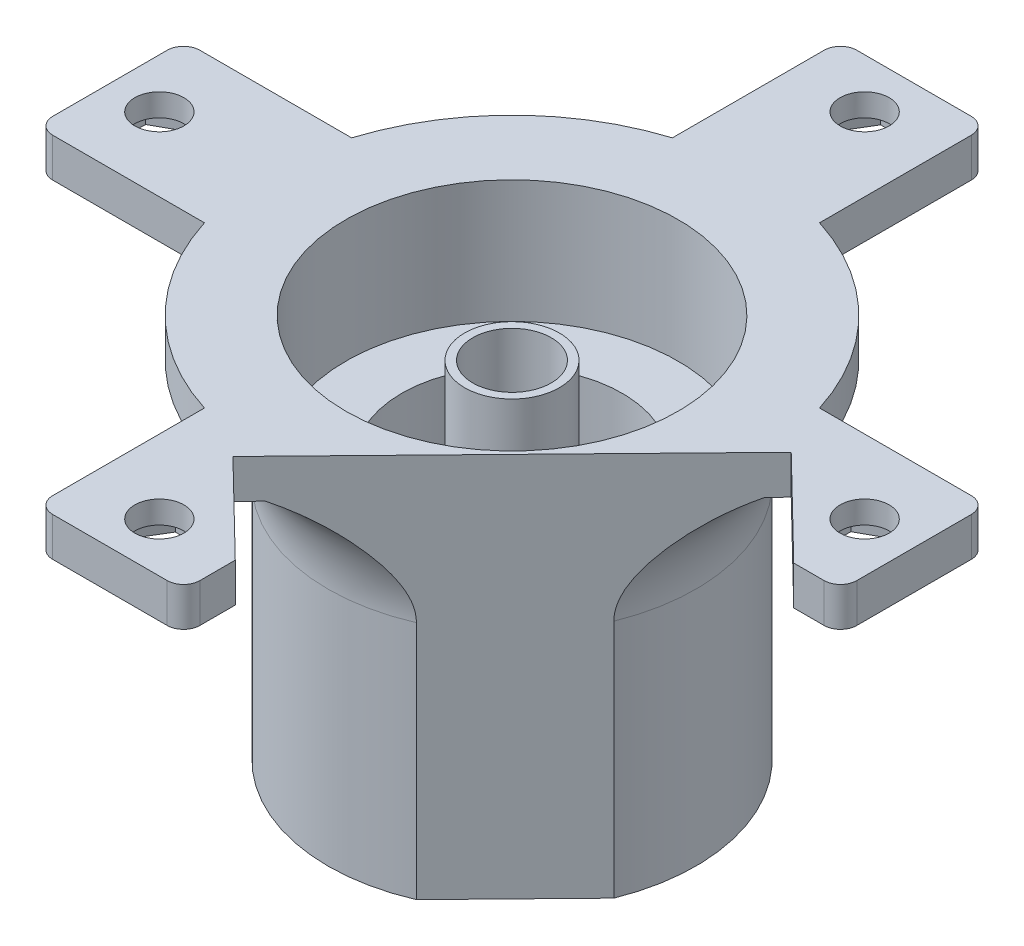
SolidWorks part; units mm, degrees
ref_plane "Front Plane" through (0, 0, 0) normal (0, 0, 1) x (1, 0, 0)
ref_plane "Top Plane" through (0, 0, 0) normal (0, 1, 0) x (1, 0, 0)
ref_plane "Right Plane" through (0, 0, 0) normal (1, 0, 0) x (0, 0, -1)
sketch "Sketch1" plane through (0, 0, 0) normal (0, 1, 0) x (1, 0, 0)
  circle A1 centre (0, 0) radius 22.5
  dimension "D2" = 45
extrude "Boss-Extrude1" add sketch "Sketch1" along normal blind 20
sketch "Sketch2" plane through (0, 20, 0) normal (0, 1, 0) x (1, 0, 0)
  circle A0 centre (0, 0) radius 22.5
  circle A1 centre (0, 0) radius 13.5
  dimension "D1" = 27
extrude "Boss-Extrude2" add sketch "Sketch2" along normal blind 20
sketch "Sketch3" plane through (0, 20, 0) normal (0, 1, 0) x (1, 0, 0)
  circle A0 centre (0, 0) radius 5.93
  dimension "D1" = 11.86
extrude "Cut-Extrude2" cut sketch "Sketch3" against normal blind 30
sketch "Sketch5" plane through (0, 0, 0) normal (0, -1, 0) x (1, 0, 0)
  line L1 (-28.6757, -6.397) -> (1.4133, -6.397)
  line L2 (-28.6757, -6.397) -> (-28.6757, 6.3734)
  line L3 (-28.6757, 6.3734) -> (1.4133, 6.3734)
  line L4 (1.4133, -6.397) -> (1.4133, 6.3734)
extrude "Cut-Extrude3" cut sketch "Sketch5" against normal blind 20
fillet "Fillet1" radius 10 2 edges at (-16.7298, 20, -6.397) (-16.7396, 20, 6.3734)
sketch "Sketch6" plane through (0, 0, 0) normal (0, -1, 0) x (1, 0, 0)
  circle A0 centre (0, 0) radius 22.5
extrude "Boss-Extrude3" add sketch "Sketch6" along normal blind 2.33
sketch "Sketch7" plane through (0, 0, 0) normal (0, 1, 0) x (1, 0, 0)
  circle A0 centre (0, 0) radius 5.8
  circle A1 centre (0, 0) radius 4.8
  dimension "D1" = 11.6
  dimension "D2" = 9.6
extrude "Boss-Extrude4" add sketch "Sketch7" along normal through all
sketch "Sketch8" plane through (0, 40, 0) normal (0, 1, 0) x (1, 0, 0)
  circle A0 centre (0, 0) radius 16
  circle A1 centre (0, 0) radius 30
  dimension "D1" = 32
  dimension "D2" = 60
extrude "Boss-Extrude5" add sketch "Sketch8" along normal blind 4.76
fillet "Fillet3" radius 15 1 edges at (0, 40, 22.5)
sketch "Sketch9" plane through (0, 44.76, 0) normal (0, 1, 0) x (1, 0, 0)
  line L0 (0, 0) -> (75.4489, 0)
  line L1 (75.4489, 0) -> (-71.7092, 0)
  line L2 (-71.7092, 0) -> (0, 0)
  line L3 (0, 0) -> (0, 61.7625)
  line L4 (0, 61.7625) -> (0, -54.9617)
  line L5 (24.1753, -9) -> (49.1753, -9)
  line L6 (9, 24.1753) -> (-9, 24.1753)
  line L7 (9, 24.1753) -> (9, 49.1753)
  line L8 (9, 49.1753) -> (-9, 49.1753)
  line L9 (-9, 24.1753) -> (-9, 49.1753)
  line L10 (24.1753, -9) -> (24.1753, 9)
  line L11 (24.1753, 9) -> (49.1753, 9)
  line L12 (49.1753, -9) -> (49.1753, 9)
  line L13 (-9, -24.1753) -> (-9, -49.1753)
  line L14 (-9, -24.1753) -> (9, -24.1753)
  line L15 (9, -24.1753) -> (9, -49.1753)
  line L16 (-9, -49.1753) -> (9, -49.1753)
  line L17 (-24.1753, 9) -> (-49.1753, 9)
  line L18 (-24.1753, 9) -> (-24.1753, -9)
  line L19 (-24.1753, -9) -> (-49.1753, -9)
  line L20 (-49.1753, 9) -> (-49.1753, -9)
  point P26 (0, 0)
  circle M7 centre (0, 0) radius 30
  dimension "D1" = 18
  dimension "D2" = 9
  dimension "D3" = 25
  dimension "D4" = 4
extrude "Boss-Extrude6" add sketch "Sketch9" against normal blind 4.76 contours L7 L8 L3 M7 | L9 L3 L8 M7 | L0 L12 L11 M7 | L5 L12 L0 M7 | L4 L16 L15 M7 | L13 L16 L4 M7 | L1 L20 L19 M7 | L17 L20 L1 M7 region at (39.3552, 44.76, -4.5525) region at (39.3552, 44.76, 4.5525) region at (-39.3552, 44.76, 4.5525) region at (-39.3552, 44.76, -4.5525) region at (-4.5525, 44.76, -39.3552) region at (4.5525, 44.76, -39.3552) region at (4.5525, 44.76, 39.3552) region at (-4.5525, 44.76, 39.3552)
sketch "Sketch13" plane through (0, 44.76, 0) normal (0, 1, 0) x (1, 0, 0)
  line L0 (0, 0) -> (0, 1.6172)
  line L1 (0, 43.1335) -> (0, -53.1995)
  line L2 (0, 0) -> (-52.7252, 0)
  line L3 (0, 0) -> (43.1335, 0)
  line L4 (43.1335, 0) -> (0, 43.1335)
  circle A0 centre (0, 43.1335) radius 3
  circle A1 centre (43.1335, 0) radius 3
  circle A2 centre (0, -43.1335) radius 3
  circle A3 centre (-43.1335, 0) radius 3
  point P18 (0, 0)
  dimension "D3" = 6
  dimension "D1" = 61
  dimension "D2" = 45
  dimension "D4" = 4
extrude "Cut-Extrude6" cut sketch "Sketch13" against normal blind 4.76 contours L1 A2 | L1 A2 | L2 A3 | L2 A3 | L3 A1 L4 | L4 A0 L1 | L1 A0 L4 | L4 A1 L3 region at (1.2732, 44.76, 43.1335) region at (-1.2732, 44.76, 43.1335) region at (-43.1335, 44.76, 1.2732) region at (-43.1335, 44.76, -1.2732) region at (41.3329, 44.76, -0.7458) region at (43.3907, 44.76, 0.1065) region at (-0.1065, 44.76, -43.3907) region at (0.7458, 44.76, -41.3329)
sketch "Sketch14" plane through (0, 44.76, 0) normal (0, 1, 0) x (1, 0, 0)
  circle A0 centre (0, 0) radius 20.32
  circle A1 centre (0, 0) radius 10
  dimension "D1" = 40.64
  dimension "D2" = 20
extrude "Cut-Extrude7" cut sketch "Sketch14" against normal blind 15
sketch "Sketch15" plane through (0, 20, 0) normal (0, 1, 0) x (1, 0, 0)
  circle A0 centre (0, 0) radius 13.5
  circle A1 centre (0, 0) radius 5.8
  circle A2 centre (0, 0) radius 5.8 construction
  dimension "D1" = 0
extrude "Cut-Extrude8" cut sketch "Sketch15" against normal blind 10
sketch "Sketch17" plane through (0, 44.76, 0) normal (0, 1, 0) x (1, 0, 0)
  line L0 (34.212, 0.0099) -> (0.5146, -34.5837)
  line L1 (34.212, 0.0099) -> (45.4754, -10.9617)
  line L2 (0.5146, -34.5837) -> (11.7781, -45.5554)
  line L3 (45.4754, -10.9617) -> (11.7781, -45.5554)
  arc A0 (-28.6182, -9) -> (-9, -28.6182) centre (0, 0) ccw construction
  dimension "D1" = 24.5
extrude "Cut-Extrude10" cut sketch "Sketch17" against normal through all
sketch "Sketch18" plane through (0, 40, 0) normal (0, -1, 0) x (-1, 0, 0)
  line L0 (47.4916, -2.3902) -> (47.3825, 2.5791)
  line L1 (2.3902, 47.4916) -> (-2.5791, 47.3825)
  line L2 (-2.5791, 47.3825) -> (-4.9693, 43.0244)
  line L3 (-4.9693, 43.0244) -> (-2.3902, 38.7754)
  line L4 (-2.3902, 38.7754) -> (2.5791, 38.8845)
  line L5 (2.5791, 38.8845) -> (4.9693, 43.2426)
  line L6 (4.9693, 43.2426) -> (2.3902, 47.4916)
  line L7 (47.3825, 2.5791) -> (43.0244, 4.9693)
  line L8 (43.0244, 4.9693) -> (38.7754, 2.3902)
  line L9 (38.7754, 2.3902) -> (38.8845, -2.5791)
  line L10 (38.8845, -2.5791) -> (43.2426, -4.9693)
  line L11 (43.2426, -4.9693) -> (47.4916, -2.3902)
  line L12 (-2.3902, -47.4916) -> (2.5791, -47.3825)
  line L13 (2.5791, -47.3825) -> (4.9693, -43.0244)
  line L14 (4.9693, -43.0244) -> (2.3902, -38.7754)
  line L15 (2.3902, -38.7754) -> (-2.5791, -38.8845)
  line L16 (-2.5791, -38.8845) -> (-4.9693, -43.2426)
  line L17 (-4.9693, -43.2426) -> (-2.3902, -47.4916)
  line L18 (-47.4916, 2.3902) -> (-47.3825, -2.5791)
  line L19 (-47.3825, -2.5791) -> (-43.0244, -4.9693)
  line L20 (-43.0244, -4.9693) -> (-38.7754, -2.3902)
  line L21 (-38.7754, -2.3902) -> (-38.8845, 2.5791)
  line L22 (-38.8845, 2.5791) -> (-43.2426, 4.9693)
  line L23 (-43.2426, 4.9693) -> (-47.4916, 2.3902)
  circle A0 centre (0, 43.1335) radius 4.3046 construction
  point P30 (0, 0)
  dimension "D1" = 4
extrude "Cut-Extrude11" cut sketch "Sketch18" against normal blind 2
sketch "Sketch19" plane through (0, 0, 0) normal (0, 1, 0) x (1, 0, 0)
  line L0 (-11.8882, 6.397) -> (1.4133, 6.397) construction
  line L1 (-8.4523, 6.397) -> (-1.4383, 6.397)
  line L2 (-8.4523, 6.397) -> (-8.4523, -6.3734)
  line L3 (-8.4523, -6.3734) -> (-1.4383, -6.3734)
  line L4 (-1.4383, 6.397) -> (-1.4383, -6.3734)
  line L5 (1.4133, -6.3734) -> (-21.5784, -6.3734) construction
  dimension "D1" = 0
  dimension "D2" = 0
extrude "Cut-Extrude13" cut sketch "Sketch19" along direction (0, 1, 0) on the side of the normal up to surface (10 mm away) up to face at (1.9625, 10, -0.0037)
fillet "Fillet4" radius 2 8 edges at (-9, 42.38, -49.1753) (9, 42.38, -49.1753) (49.1753, 42.38, -9) (49.1753, 42.38, 9) (9, 42.38, 49.1753) (-9, 42.38, 49.1753) (-49.1753, 42.38, 9) (-49.1753, 42.38, -9)
sketch "Sketch20" plane through (0, 44.76, 0) normal (0, 1, 0) x (1, 0, 0)
  line L0 (0.5146, -34.5837) -> (34.212, 0.0099)
  line L1 (0.5146, -34.5837) -> (-2.1236, -32.0139)
  line L2 (34.212, 0.0099) -> (31.5737, 2.5798)
  line L3 (-2.1236, -32.0139) -> (31.5737, 2.5798)
extrude "Cut-Extrude15" cut sketch "Sketch20" along direction (0, -1, 0) on the side against the normal up to surface (47.09 mm away) up to face at (0, -2.33, -22.5)
sketch "Sketch22" plane through (0, 0, 0) normal (0, 1, 0) x (1, 0, 0)
  line L0 (-1.4383, 4.5794) -> (-1.4383, 6.4099)
  line L1 (-1.4383, 6.4099) -> (-1.4383, -6.4099)
  circle A0 centre (0, 0) radius 5.8
  circle A1 centre (0, 0) radius 6.5693
  arc A2 (-1.4383, -5.6188) -> (-1.4383, 5.6188) centre (0, 0) ccw construction
  arc M6 (-1.4383, 5.6188) -> (-1.4383, -5.6188) centre (0, 0) cw
  line M10 (1.4133, 5.7591) -> (1.4133, 6.397)
  line M11 (1.4133, 6.397) -> (-21.5715, 6.397)
  line M13 (-21.5784, -6.3734) -> (1.4133, -6.3734)
  line M14 (1.4133, -6.3734) -> (1.4133, -5.7591)
  arc M15 (1.4133, -5.7591) -> (1.4133, 5.7591) centre (0, 0) ccw
  dimension "D1" = 0
extrude "Boss-Extrude7" add sketch "Sketch22" along normal up to surface (10 mm away) contours L1 L0 M6 M13 M14 M15 M10 M11 region at (-1.2909, 0, -6.0079) up to face at (1.9625, 10, -0.0037)
fillet "Fillet5" radius 40 2 edges at (-1.4383, 5, 6.3734) (-1.4383, 5, -6.397)
fillet "Fillet6" radius 9 2 edges at (-2.1792, 10, 4.8013) (-2.1774, 10, -4.8024)
fillet "Fillet7" radius 6 2 edges at (-2.9243, 5.5, 5.0088) (-2.9206, 5.5, -5.011)
